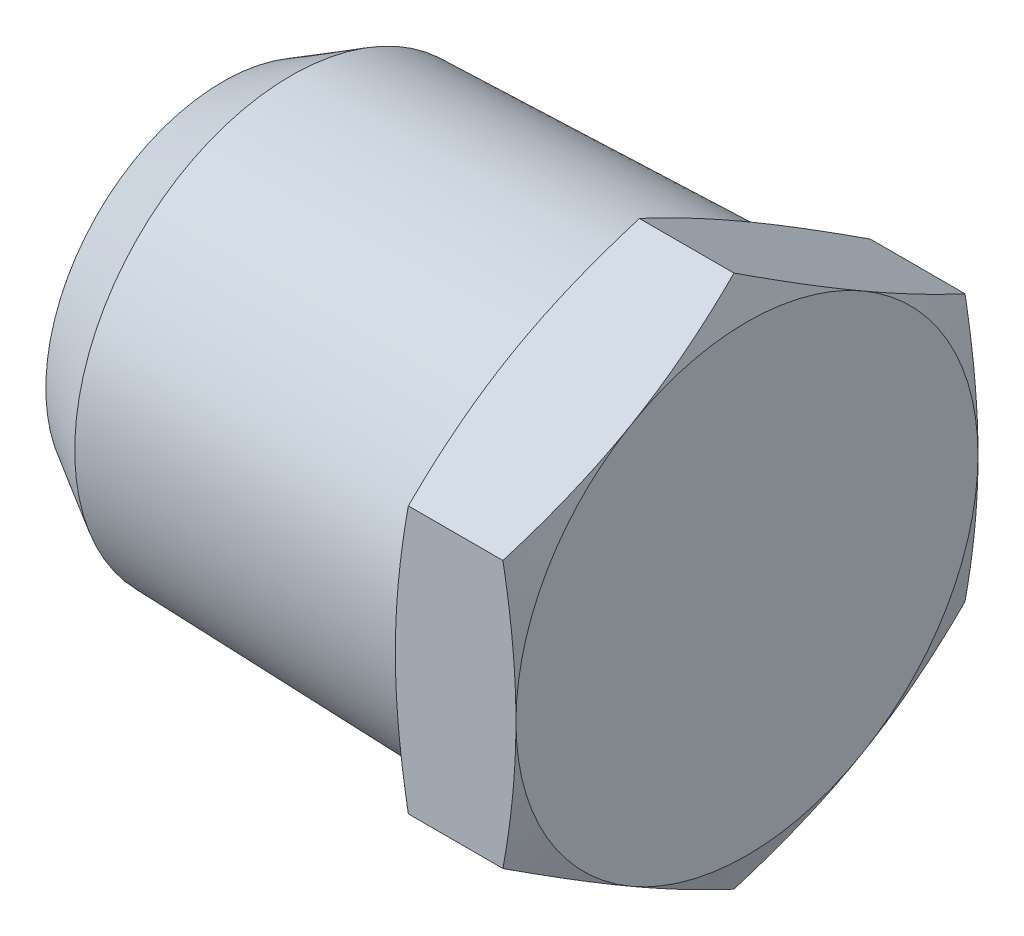
SolidWorks part; units mm, degrees
ref_plane "Front" through (0, 0, 0) normal (0, 0, 1) x (1, 0, 0)
ref_plane "Top" through (0, 0, 0) normal (0, 1, 0) x (1, 0, 0)
ref_plane "Right" through (0, 0, 0) normal (1, 0, 0) x (0, 0, -1)
sketch "Sketch1" plane through (0, 0, 0) normal (0, 0, 1) x (1, 0, 0)
  line L0 (-9.906, 0) -> (9.906, 0) construction
  point P3 (5.3492, 0)
ref_plane "Plane1" through (5.3492, 0, 0) normal (1, 0, 0) x (0, 0, -1)
sketch "Sketch2" plane through (5.3492, 0, 0) normal (1, 0, 0) x (0, 0, -1)
  circle A0 centre (0, 0) radius 8.5725
  dimension "pipe OD" = 17.145
extrude "Extrude1" add sketch "Sketch2" against normal up to vertex (15.2552 mm away) draft 1.783 up to point (-9.906, 0, 0)
sketch "Sketch6" plane through (5.3492, 0, 0) normal (1, 0, 0) x (0, 0, -1)
  circle A0 centre (0, 0) radius 8.5725 construction
  circle A1 centre (0, 0) radius 8.5725
curve "Helix/Spiral1" parameters "pitch"=1.4111
chamfer "Chamfer1" distance 1.4111 angle 60 1 edges at (-9.906, 0, -8.0975) first distance on face at (-9.906, 0, -8.0975)
sketch "Sketch7" plane through (0, 0, 0) normal (0, 0, 1) x (1, 0, 0)
  line L0 (5.9666, -8.5725) -> (5.4374, -7.656) construction
  line L1 (5.4374, -7.656) -> (5.261, -7.656)
  line L2 (5.261, -7.656) -> (4.7319, -8.5725)
  line L3 (5.9666, -8.5725) -> (4.7319, -8.5725) construction
  line L4 (5.3492, -8.5725) -> (5.3492, -7.656) construction
  line L5 (5.702, -8.1142) -> (4.9965, -8.1142) construction
  line L6 (4.7319, -8.5725) -> (6.1065, -8.8149)
  line L7 (6.1065, -8.8149) -> (5.4374, -7.656)
  line L8 (3.8346, -8.8149) -> (5.3492, -8.8149) construction
  line L9 (5.3492, -8.5725) -> (5.3492, 8.5725) construction
  line L10 (4.7319, -8.5725) -> (4.5919, -8.8149) construction
  line L11 (4.5919, -8.8149) -> (6.1065, -8.8149) construction
  line L12 (3.8346, -8.8149) -> (2.32, -8.8149) construction
  line L13 (2.32, -8.8149) -> (0.8054, -8.8149) construction
  line L14 (0.8054, -8.8149) -> (-0.7092, -8.8149) construction
  line L15 (-0.7092, -8.8149) -> (-2.2238, -8.8149) construction
  line L16 (-2.2238, -8.8149) -> (-3.7384, -8.8149) construction
  line L17 (-3.7384, -8.8149) -> (-5.253, -8.8149) construction
  line L18 (-5.253, -8.8149) -> (-5.253, -8.2424) construction
  line L19 (-7.3226, -8.178) -> (5.3492, -8.5725) construction
  line L20 (-3.7384, -8.8149) -> (-3.7384, -8.2896) construction
  dimension "D1" = 60
  dimension "D2" = 0.1764
  dimension "D3" = 0.7056
  dimension "D4" = 10
sweep "Cut-Sweep1" [suppressed] cut profiles "Sketch7" path "Helix/Spiral1"
sketch "Sketch3" plane through (5.3492, 0, 0) normal (-1, 0, 0) x (0, 0, 1)
  line L1 (8.7312, 5.041) -> (0, 10.082)
  line L2 (0, 10.082) -> (-8.7312, 5.041)
  line L3 (-8.7312, 5.041) -> (-8.7312, -5.041)
  line L4 (-8.7312, -5.041) -> (0, -10.082)
  line L5 (0, -10.082) -> (8.7312, -5.041)
  line L6 (8.7312, -5.041) -> (8.7312, 5.041)
  circle A0 centre (0, 0) radius 8.7312 construction
  dimension "Hex" = 17.4625
extrude "Extrude2" add sketch "Sketch3" against normal up to vertex (4.5568 mm away) up to point (9.906, 0, 0)
sketch "Sketch4" plane through (9.906, 0, 0) normal (1, 0, 0) x (0, 0, -1)
  circle A0 centre (0, 0) radius 8.7312 construction
  circle A1 centre (0, 0) radius 8.7312
extrude "Cut-Extrude1" cut sketch "Sketch4" against normal through all draft 70 flip side to cut
sketch "Sketch10" plane through (5.3492, 0, 0) normal (-1, 0, 0) x (0, 0, 1)
  circle A0 centre (0, 0) radius 8.7312 construction
  circle A1 centre (0, 0) radius 8.7312
extrude "Cut-Extrude2" cut sketch "Sketch10" against normal through all draft 70 flip side to cut
sketch "Sketch12" plane through (0, 0, 0) normal (0, 0, 1) x (1, 0, 0)
  line L0 (-9.906, 6.6864) -> (-9.906, -6.6864) construction
  line L1 (-9.906, 0) -> (6.7359, 0)
  line L2 (-9.906, 0) -> (-9.906, 5.715)
  line L3 (-9.906, 5.715) -> (3.302, 5.715)
  line L4 (6.7359, 0) -> (3.302, 5.715)
  line L5 (6.7359, 0) -> (9.906, 0) construction
  dimension "D1" = 59
  dimension "D2" = 11.43
  dimension "D3" = 13.208
revolve "Cut-Revolve1" cut sketch "Sketch12" angle 360 about L5
equation "\"D3@Helix/Spiral1\" = \"G@Sketch1\" + 1/4"
equation "\"D2@Sketch7\" = \"pitch@Helix/Spiral1\" * 1/8"
equation "\"D3@Sketch7\" = \"pitch@Helix/Spiral1\" * 1/2"
equation "\"D1@Chamfer1\" = \"pitch@Helix/Spiral1\""
equation "\"D2@Sketch12\" = \"pipe OD@Sketch2\" * 2 / 3"
equation "\"D3@Sketch12\" = \"L@Sketch1\" * 2 / 3"
